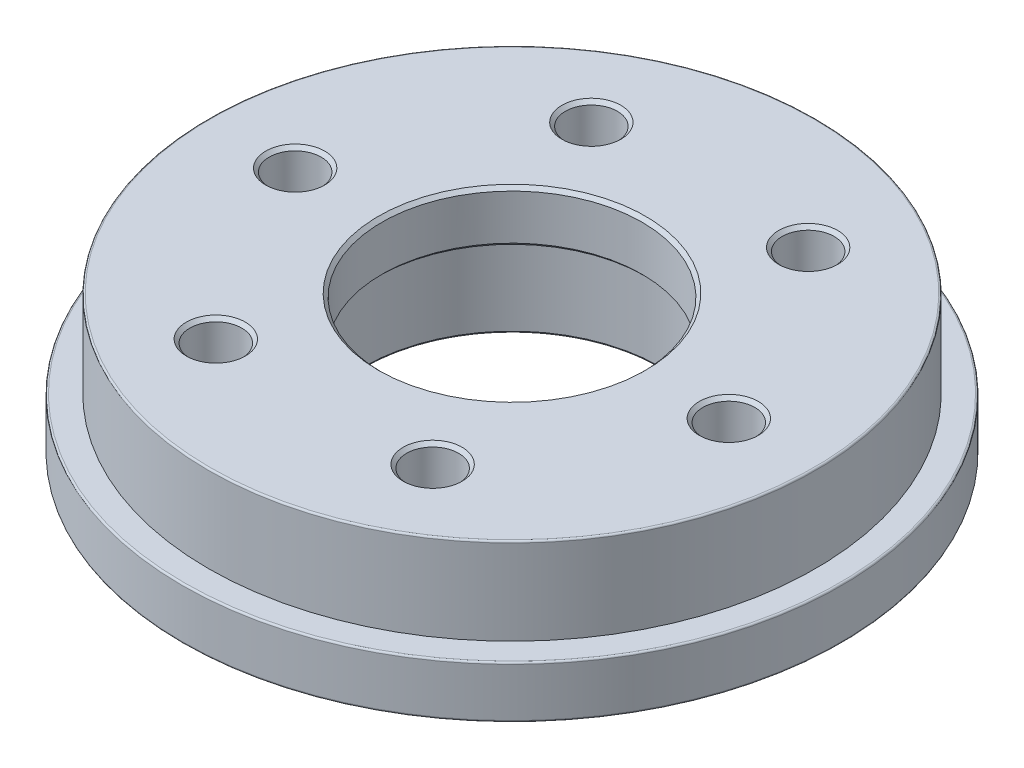
SolidWorks part; units mm, degrees
ref_plane "前视基准面" through (0, 0, 0) normal (0, 0, 1) x (1, 0, 0)
ref_plane "上视基准面" through (0, 0, 0) normal (0, 1, 0) x (1, 0, 0)
ref_plane "右视基准面" through (0, 0, 0) normal (1, 0, 0) x (0, 0, -1)
other "Configuration Table"
sketch "草图1" plane through (0, 0, 0) normal (0, 1, 0) x (1, 0, 0)
  circle A0 centre (0, 0) radius 19
  circle A1 centre (0, 0) radius 15 construction
  circle A2 centre (0, 15) radius 3.05
  circle A3 centre (12.9904, 7.5) radius 3.05
  circle A4 centre (12.9904, -7.5) radius 3.05
  circle A5 centre (0, -15) radius 3.05
  circle A6 centre (-12.9904, -7.5) radius 3.05
  circle A7 centre (-12.9904, 7.5) radius 3.05
  point P18 (0, 0)
  dimension "D1" = 6.1
  dimension "D2" = 38
  dimension "D3" = 30
  dimension "D4" = 6
extrude "凸台-拉伸1" add sketch "草图1" along normal blind 3 contours A0
extrude "切除-拉伸1" cut sketch "草图1<3>" along normal blind 1.5 contours A7 | A6 | A5 | A4 | A3 | A2 region at (0, 0, -15) region at (12.9904, 0, -7.5) region at (12.9904, 0, 7.5) region at (0, 0, 15) region at (-12.9904, 0, 7.5) region at (-12.9904, 0, -7.5)
sketch "草图1<3>" plane through (0, 0, 0) normal (0, 1, 0) x (1, 0, 0) same geometry as "草图1"
sketch "草图5" plane through (0, 3, 0) normal (0, 1, 0) x (1, 0, 0)
  circle A1 centre (0, 0) radius 17.5
  dimension "D1" = 35
extrude "凸台-拉伸3" add sketch "草图5" along normal blind 5
sketch "草图7" plane through (0, 0, 0) normal (0, -1, 0) x (1, 0, 0)
  circle A0 centre (0, 0) radius 8.5
  dimension "D1" = 17
extrude "切除-拉伸2" cut sketch "草图7" against normal blind 5
sketch "草图8" plane through (0, 5, 0) normal (0, -1, 0) x (1, 0, 0)
  circle A0 centre (0, 0) radius 7.5
  dimension "D1" = 15
extrude "切除-拉伸3" cut sketch "草图8" against normal blind 0.5
sketch "草图10" plane through (0, 0, 0) normal (0, -1, 0) x (1, 0, 0)
  line L0 (0, 15) -> (12.9904, 7.5) construction
  line L2 (6.25, 10.8253) -> (0, 0) construction
  circle A0 centre (0, 0) radius 12.5 construction
  circle A1 centre (6.25, 10.8253) radius 1.5
  circle A2 centre (12.5, 0) radius 1.5
  circle A3 centre (6.25, -10.8253) radius 1.5
  circle A4 centre (-6.25, -10.8253) radius 1.5
  circle A5 centre (-12.5, 0) radius 1.5
  circle A6 centre (-6.25, 10.8253) radius 1.5
  point P21 (0, 0)
  dimension "D1" = 3
  dimension "D3" = 25
  dimension "D2" = 6
extrude "切除-拉伸4" cut sketch "草图10" against normal up to next
sketch "草图11" plane through (0, 0, 0) normal (0, -1, 0) x (1, 0, 0)
  line L0 (6.25, -14.0007) -> (9, -12.413)
  line L1 (15.25, -1.5877) -> (15.25, 1.5877)
  line L2 (15.25, 1.5877) -> (12.5, 3.1754)
  line L3 (12.5, 3.1754) -> (9.75, 1.5877)
  line L4 (9.75, 1.5877) -> (9.75, -1.5877)
  line L5 (9.75, -1.5877) -> (12.5, -3.1754)
  line L6 (12.5, -3.1754) -> (15.25, -1.5877)
  line L7 (9, -12.413) -> (9, -9.2376)
  line L8 (9, -9.2376) -> (6.25, -7.6499)
  line L9 (6.25, -7.6499) -> (3.5, -9.2376)
  line L10 (3.5, -9.2376) -> (3.5, -12.413)
  line L11 (3.5, -12.413) -> (6.25, -14.0007)
  line L12 (-9, -12.413) -> (-6.25, -14.0007)
  line L13 (-6.25, -14.0007) -> (-3.5, -12.413)
  line L14 (-3.5, -12.413) -> (-3.5, -9.2376)
  line L15 (-3.5, -9.2376) -> (-6.25, -7.6499)
  line L16 (-6.25, -7.6499) -> (-9, -9.2376)
  line L17 (-9, -9.2376) -> (-9, -12.413)
  line L18 (-15.25, 1.5877) -> (-15.25, -1.5877)
  line L19 (-15.25, -1.5877) -> (-12.5, -3.1754)
  line L20 (-12.5, -3.1754) -> (-9.75, -1.5877)
  line L21 (-9.75, -1.5877) -> (-9.75, 1.5877)
  line L22 (-9.75, 1.5877) -> (-12.5, 3.1754)
  line L23 (-12.5, 3.1754) -> (-15.25, 1.5877)
  line L24 (-6.25, 14.0007) -> (-9, 12.413)
  line L25 (-9, 12.413) -> (-9, 9.2376)
  line L26 (-9, 9.2376) -> (-6.25, 7.6499)
  line L27 (-6.25, 7.6499) -> (-3.5, 9.2376)
  line L28 (-3.5, 9.2376) -> (-3.5, 12.413)
  line L29 (-3.5, 12.413) -> (-6.25, 14.0007)
  line L30 (9, 12.413) -> (6.25, 14.0007)
  line L31 (6.25, 14.0007) -> (3.5, 12.413)
  line L32 (3.5, 12.413) -> (3.5, 9.2376)
  line L33 (3.5, 9.2376) -> (6.25, 7.6499)
  line L34 (6.25, 7.6499) -> (9, 9.2376)
  line L35 (9, 9.2376) -> (9, 12.413)
  circle A0 centre (12.5, 0) radius 2.75 construction
  point P41 (0, 0)
  dimension "D1" = 5.5
  dimension "D2" = 6
extrude "切除-拉伸5" cut sketch "草图11" against normal blind 2
sketch "草图12" plane through (0, 8, 0) normal (0, 1, 0) x (1, 0, 0)
  circle A0 centre (0, 0) radius 7.5
  dimension "D1" = 15
extrude "切除-拉伸6" cut sketch "草图12" against normal up to next
chamfer "倒角1" distance 0.2 angle 45 14 edges at (-12.5, 2, -1.5) (-12.5, 8, 1.5) (-6.25, 2, 9.3253) (-6.25, 8, 12.3253) (6.25, 2, 9.3253) (6.25, 8, 12.3253) (12.5, 2, -1.5) (12.5, 8, 1.5) (6.25, 2, -12.3253) (6.25, 8, -9.3253) (-6.25, 2, -12.3253) (-6.25, 8, -9.3253) (0, 8, 7.5) (0, 5, -7.5)
fillet "圆角1" radius 0.1 4 edges at (0, 0, 19) (0, 3, 19) (0, 0, -8.5) (0, 8, 17.5)
fillet "圆角2" radius 0.1 6 edges at (12.9904, 0, 10.55) (12.9904, 0, -4.45) (0, 0, -11.95) (-12.9904, 0, -4.45) (-12.9904, 0, 10.55) (0, 0, 18.05)
